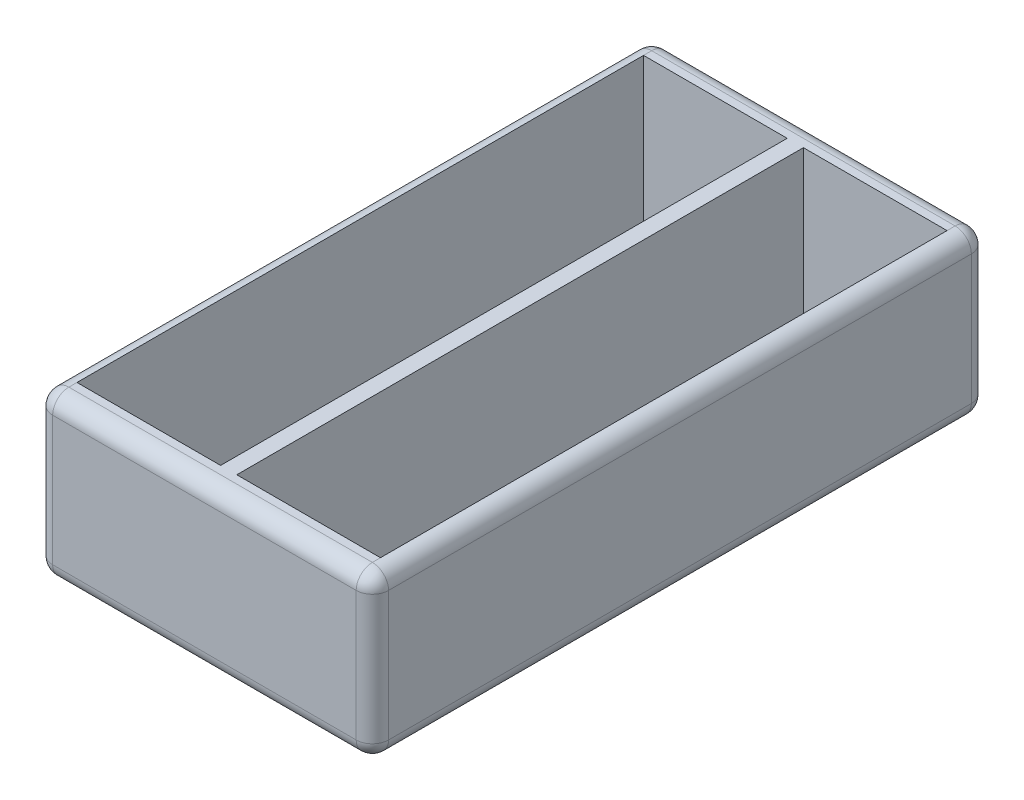
SolidWorks part; units mm, degrees
ref_plane "前视基准面" through (0, 0, 0) normal (0, 0, 1) x (1, 0, 0)
ref_plane "上视基准面" through (0, 0, 0) normal (0, 1, 0) x (1, 0, 0)
ref_plane "右视基准面" through (0, 0, 0) normal (1, 0, 0) x (0, 0, -1)
sketch "草图1" plane through (0, 0, 0) normal (0, 1, 0) x (1, 0, 0)
  line L1 (-20.75, -38) -> (20.75, -38)
  line L2 (-20.75, -38) -> (-20.75, 38)
  line L3 (-20.75, 38) -> (20.75, 38)
  line L4 (20.75, -38) -> (20.75, 38)
  line L5 (0, 38) -> (0, -38) construction
  line L6 (-20.75, 0) -> (20.75, 0) construction
  point P0 (0, 0)
  dimension "D1" = 76
  dimension "D2" = 41.5
extrude "凸台-拉伸1" add sketch "草图1" along normal blind 20
sketch "草图2" plane through (0, 20, 0) normal (0, 1, 0) x (1, 0, 0)
  line L0 (0, 42.9848) -> (0, -49.8624) construction
  line L1 (-20.75, 38) -> (-20.75, -38) construction
  line L2 (-1, 35) -> (-18.75, 35)
  line L3 (-1, 35) -> (-1, -35)
  line L4 (-1, -35) -> (-18.75, -35)
  line L5 (-18.75, 35) -> (-18.75, -35)
  line L6 (20.75, 38) -> (-20.75, 38) construction
  line L7 (-20.75, -38) -> (20.75, -38) construction
  line L8 (18.75, 35) -> (18.75, -35)
  line L9 (1, -35) -> (18.75, -35)
  line L10 (1, 35) -> (1, -35)
  line L11 (1, 35) -> (18.75, 35)
  dimension "D1" = 1
  dimension "D2" = 2
  dimension "D3" = 3
  dimension "D4" = 3
extrude "切除-拉伸1" cut sketch "草图2" against normal blind 19
sketch "草图3" plane through (0, 1, 0) normal (0, 1, 0) x (1, 0, 0)
  line L0 (0, 0) -> (0, 11.2528) construction
  line L1 (0, 0) -> (-20.75, 0) construction
  line L2 (-20.75, 38) -> (-20.75, -38) construction
  circle A0 centre (-8.85, 0) radius 1.6
  circle A1 centre (8.85, 0) radius 1.6
  dimension "D1" = 3.2
  dimension "D2" = 8.85
extrude "切除-拉伸2" cut sketch "草图3" against normal blind 19
fillet "圆角1" radius 2 12 edges at (0, 20, 38) (-20.75, 10, 38) (-20.75, 20, 0) (-20.75, 0, 0) (20.75, 10, -38) (0, 20, -38) (-20.75, 10, -38) (0, 0, -38) (20.75, 20, 0) (20.75, 0, 0) (0, 0, 38) (20.75, 10, 38)
